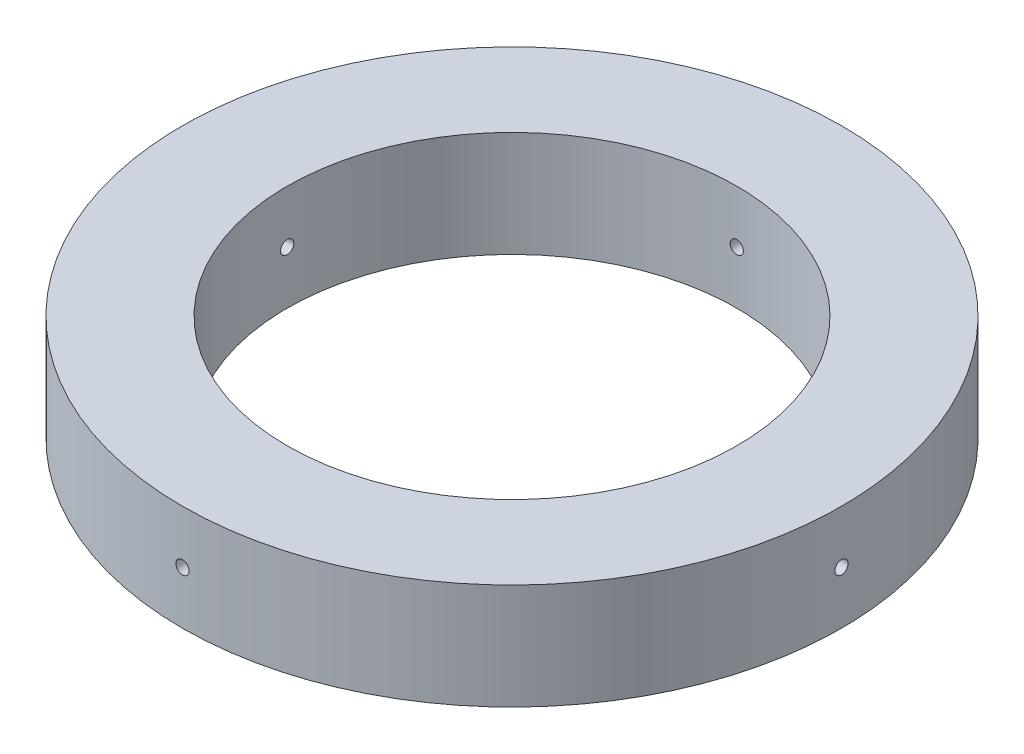
SolidWorks part; units mm, degrees
ref_plane "Front Plane" through (0, 0, 0) normal (0, 0, 1) x (1, 0, 0)
ref_plane "Top Plane" through (0, 0, 0) normal (0, 1, 0) x (1, 0, 0)
ref_plane "Right Plane" through (0, 0, 0) normal (1, 0, 0) x (0, 0, -1)
sketch "Croquis1" plane through (0, 0, 0) normal (0, 1, 0) x (1, 0, 0)
  circle A0 centre (0, 0) radius 42.55
  circle A1 centre (0, 0) radius 62.36
  dimension "D1" = 85.1
  dimension "D2" = 124.72
extrude "Saliente-Extruir1" add sketch "Croquis1" along normal blind 20
sketch "Croquis2" plane through (0, 0, 0) normal (0, 0, 1) x (1, 0, 0)
  circle A0 centre (0, 10) radius 1.25
  dimension "D2" = 2.5
  dimension "D1" = 10
extrude "Cortar-Extruir1" cut sketch "Croquis2" against normal up to surface (62.3475 mm away) up to face at (0, 20, 62.36)
pattern_circular "MatrizC1" count 4 over 360 about axis through (0, 20, 0) along (0, 1, 0) of "Cortar-Extruir1"
equation "\"D2@Croquis1\"=84.72+20*2"
